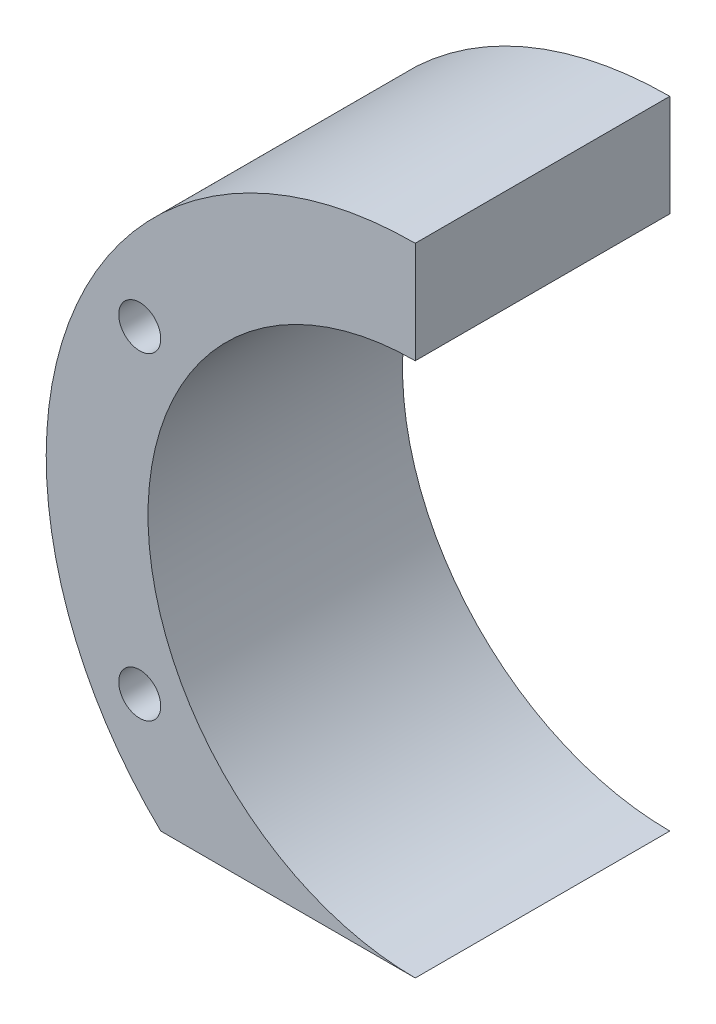
SolidWorks part; units mm, degrees
ref_plane "前视基准面" through (0, 0, 0) normal (0, 0, 1) x (1, 0, 0)
ref_plane "上视基准面" through (0, 0, 0) normal (0, 1, 0) x (1, 0, 0)
ref_plane "右视基准面" through (0, 0, 0) normal (1, 0, 0) x (0, 0, -1)
other "Configuration Table"
sketch "草图1" plane through (0, 0, 0) normal (0, 0, 1) x (1, 0, 0)
  line L0 (-20, -21) -> (0, -21)
  line L1 (0, 29) -> (0, -21) construction
  line L2 (0, 29) -> (0, 21)
  arc A0 (0, 29) -> (-20, -21) centre (0, 0) ccw
  arc A2 (0, 21) -> (0, -21) centre (0, 0) ccw
  dimension "D1" = 42
  dimension "D2" = 8
extrude "凸台-拉伸2" add sketch "草图1" along normal blind 20
sketch "草图3" plane through (0, 0, 0) normal (0, 0, 1) x (1, 0, 0)
  line L1 (-12.5, 21.6506) -> (0, 0) construction
  line L2 (0, 21) -> (0, 29) construction
  line L3 (-21.6506, 12.5) -> (0, 0) construction
  line L4 (-21.6506, -12.5) -> (0, 0) construction
  circle A0 centre (0, 0) radius 25 construction
  arc A1 (0, 21) -> (0, -21) centre (0, 0) ccw construction
  circle A2 centre (-12.5, 21.6506) radius 1.65
  circle A3 centre (-21.6506, 12.5) radius 1.65
  circle A4 centre (-21.6506, -12.5) radius 1.65
  dimension "D1" = 4
  dimension "D2" = 3.3
  dimension "D3" = 3.3
  dimension "D4" = 3.3
  dimension "D5" = 30
  dimension "D6" = 30
  dimension "D7" = 60
extrude "切除-拉伸2" cut sketch "草图3" along normal blind 20
other "删除面1" face at (-10.85, 21.6506, 20) and patch yes
